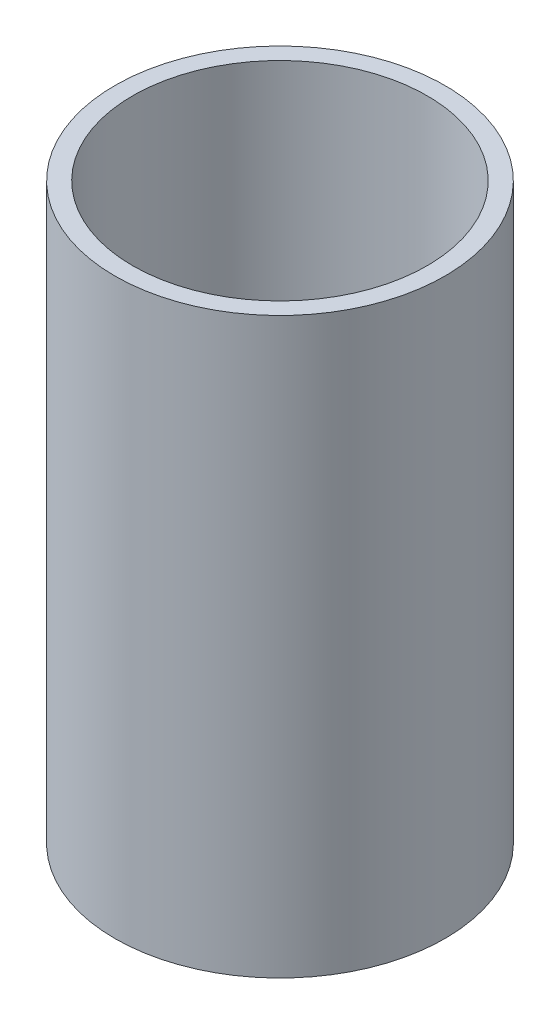
SolidWorks part; units mm, degrees
ref_plane "Front Plane" through (0, 0, 0) normal (0, 0, 1) x (1, 0, 0)
ref_plane "Top Plane" through (0, 0, 0) normal (0, 1, 0) x (1, 0, 0)
ref_plane "Right Plane" through (0, 0, 0) normal (1, 0, 0) x (0, 0, -1)
sketch "Sketch1" plane through (0, 0, 0) normal (0, 1, 0) x (1, 0, 0)
  circle A0 centre (0, 0) radius 42.5
  dimension "SLEEVE_OD" = 85
extrude "Boss-Extrude1" add sketch "Sketch1" along normal blind 147.7636
sketch "Sketch2" plane through (0, 0, 0) normal (0, 1, 0) x (1, 0, 0)
  circle A0 centre (0, 0) radius 37.9232
  dimension "BORE_D" = 75.8463
extrude "Cut-Extrude1" cut sketch "Sketch2" along normal through all
chamfer "Chamfer1" distance 2.5422 angle 60 rebuild error yes
